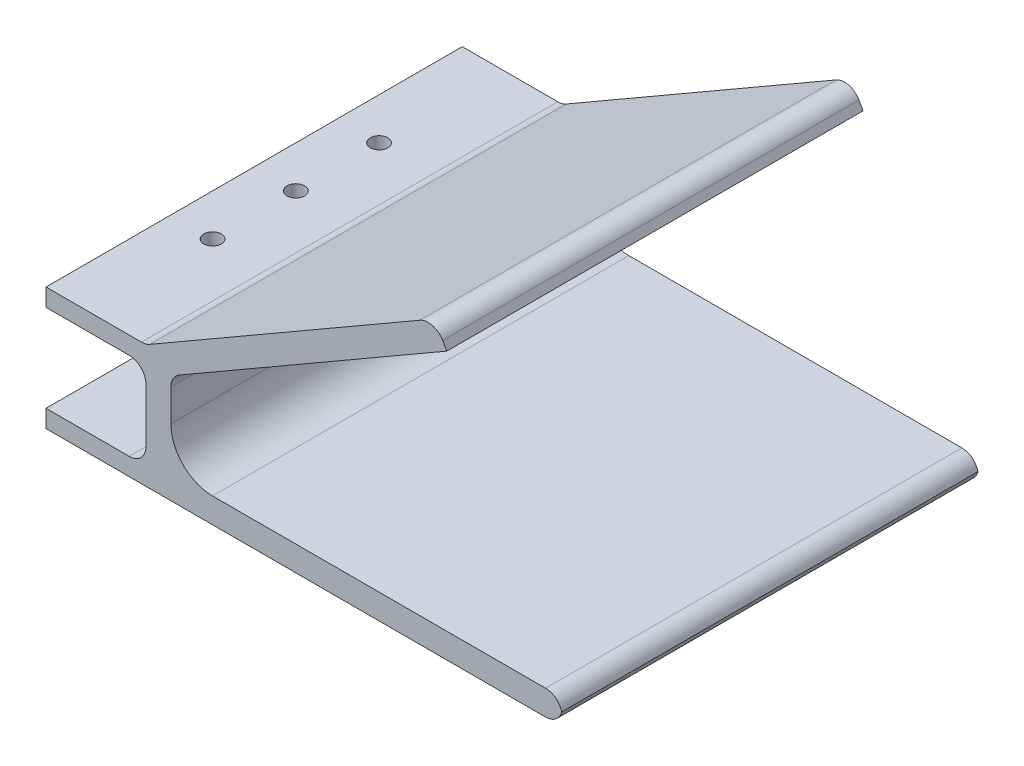
SolidWorks part; units mm, degrees
ref_plane "前视基准面" through (0, 0, 0) normal (0, 0, 1) x (1, 0, 0)
ref_plane "上视基准面" through (0, 0, 0) normal (0, 1, 0) x (1, 0, 0)
ref_plane "右视基准面" through (0, 0, 0) normal (1, 0, 0) x (0, 0, -1)
sketch "草图1" plane through (0, 0, 0) normal (0, 0, 1) x (1, 0, 0)
  line L0 (66.282, 38.2679) -> (0, 0)
  line L1 (0, 0) -> (0, -20)
  line L2 (0, -20) -> (94, -20)
  line L3 (63.282, 43.4641) -> (-6, 3.4641)
  line L4 (-6, 3.4641) -> (-6, -26)
  line L5 (-6, -26) -> (94, -26)
  line L6 (94, -20) -> (94, -26)
  line L7 (63.282, 43.4641) -> (66.282, 38.2679)
  dimension "D1" = 6
  dimension "D2" = 100
  dimension "D3" = 80
  dimension "D4" = 120
  dimension "D5" = 20
extrude "凸台-拉伸1" add sketch "草图1" along normal blind 100
fillet "圆角1" radius 4 4 edges at (94, -20, 50) (94, -26, 50) (63.282, 43.4641, 50) (0, 0, 50)
sketch "草图2" plane through (-6, 0, 0) normal (-1, 0, 0) x (0, 0, 1)
  line L0 (0, -26) -> (100, -26)
  line L1 (100, -26) -> (100, 3.4641)
  line L2 (100, 3.4641) -> (0, 3.4641)
  line L3 (0, 3.4641) -> (0, -26)
  line L4 (0, -21.7679) -> (100, -21.7679)
  line L5 (0, -0.7679) -> (100, -0.7679)
  point P12 (100, -11.2679)
  line M7 (0, 3.4641) -> (0, -26)
  line M8 (0, -26) -> (100, -26)
  line M9 (100, -26) -> (100, 3.4641)
  line M10 (100, 3.4641) -> (0, 3.4641)
  dimension "D1" = 10.5
  dimension "D2" = 21
extrude "凸台-拉伸2" add sketch "草图2" along normal blind 24 contours L5 M7 M9 M10 | L4 L3 M8 M9 region at (-6, -23.884, 50) region at (-6, 1.3481, 50)
fillet "圆角2" radius 4 2 edges at (-6, -21.7679, 50) (-6, -0.7679, 50)
fillet "圆角3" radius 4 1 edges at (-6, 3.4641, 50)
sketch "草图3" plane through (0, 3.4641, 0) normal (0, 1, 0) x (1, 0, 0)
  line L0 (-30, -100) -> (-30, 0) construction
  circle A0 centre (-20, -30) radius 2.1
  circle A1 centre (-20, -50) radius 2.1
  circle A2 centre (-20, -70) radius 2.1
  point P5 (-30, -50)
  dimension "D1" = 10
  dimension "D3" = 4.2
  dimension "D2" = 20
  dimension "D5" = 20
  dimension "D4" = 3
extrude "切除-拉伸2" cut sketch "草图3" against normal through all
fillet "圆角4" radius 10 1 edges at (0, -20, 50)
